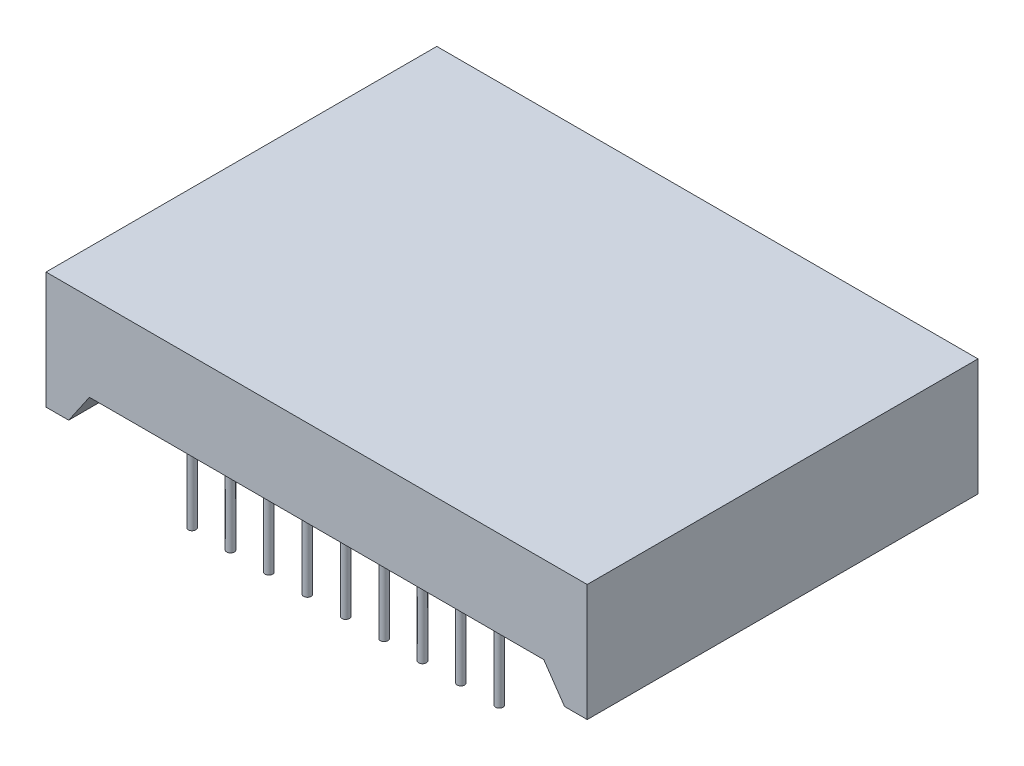
SolidWorks part; units mm, degrees
ref_plane "Front" through (0, 0, 0) normal (0, 0, 1) x (1, 0, 0)
ref_plane "Top" through (0, 0, 0) normal (0, 1, 0) x (1, 0, 0)
ref_plane "Right" through (0, 0, 0) normal (1, 0, 0) x (0, 0, -1)
sketch "Эскиз1" plane through (0, 0, 0) normal (0, 1, 0) x (1, 0, 0)
  line L0 (0, 109.8696) -> (0, -113.1116) construction
  line L1 (-69.1401, 0) -> (59.6618, 0) construction
  line L3 (17.9, -12.925) -> (-17.9, -12.925)
  line L4 (17.9, -12.925) -> (17.9, 12.925)
  line L5 (17.9, 12.925) -> (-17.9, 12.925)
  line L6 (-17.9, -12.925) -> (-17.9, 12.925)
  line L7 (17.9, -12.925) -> (-17.9, 12.925) construction
  line L8 (17.9, 12.925) -> (-17.9, -12.925) construction
  circle A0 centre (-10.16, -11) radius 0.25
  circle A1 centre (-7.62, -11) radius 0.25
  circle A2 centre (-5.08, -11) radius 0.25
  circle A3 centre (-2.54, -11) radius 0.25
  circle A4 centre (0, -11) radius 0.25
  circle A5 centre (2.54, -11) radius 0.25
  circle A6 centre (5.08, -11) radius 0.25
  circle A7 centre (7.62, -11) radius 0.25
  circle A8 centre (10.16, -11) radius 0.25
  circle A9 centre (10.16, 11) radius 0.25
  circle A10 centre (7.62, 11) radius 0.25
  circle A11 centre (5.08, 11) radius 0.25
  circle A12 centre (2.54, 11) radius 0.25
  circle A13 centre (0, 11) radius 0.25
  circle A14 centre (-2.54, 11) radius 0.25
  circle A15 centre (-5.08, 11) radius 0.25
  circle A16 centre (-7.62, 11) radius 0.25
  circle A17 centre (-10.16, 11) radius 0.25
  point P5 (0, 0)
  point P10 (0, 0)
  point P47 (0, 0)
  point P48 (0, 0)
  point P49 (0, 0)
  point P50 (0, 0)
  dimension "D3" = 0.5
  dimension "D1" = 25.85
  dimension "D2" = 35.8
  dimension "D5" = 11
  dimension "D6" = 7.74
  dimension "D4" = 9
extrude "Бобышка-Вытянуть1" add sketch "Эскиз1" along normal blind 7.74 contours L6 L3 L4 L5 A16 A14 A12 A10 A0 A1 A2 A3 A4 A5 A6 A7 A8 A9 A11 A13 A15 A17 | A0 | A1 | A2 | A3 | A4 | A5 | A6 | A7 | A8 | A17 | A16 | A15 | A14 | A13 | A12 | A11 | A10 | A9 region at (0, 0, 0)
sketch "Эскиз2" plane through (0, 0, 12.925) normal (0, 0, 1) x (1, 0, 0)
  line L0 (-17.9, 7.74) -> (-17.9, 0) construction
  line L1 (-16.4, 0) -> (-15.0276, 2)
  line L2 (-15.0276, 2) -> (15.0276, 2)
  line L3 (0, 0) -> (0, 13.6727) construction
  line L5 (16.4, 0) -> (15.0276, 2)
  point P6 (0, 0)
  point P7 (0, 0)
  point P8 (0, 0)
  point P10 (0, 0)
  point P14 (0, 2)
  dimension "D1" = 1.5
  dimension "D2" = 2
extrude "Вырез-Вытянуть1" cut sketch "Эскиз2" against normal through all and the other way through all
extrude "Бобышка-Вытянуть2" add sketch "Эскиз1<4>" against normal blind 4 and the other way up to next contours A0 | A1 | A2 | A3 | A4 | A5 | A6 | A7 | A8 | A17 | A16 | A15 | A14 | A13 | A12 | A11 | A10 | A9
sketch "Эскиз1<4>" plane through (0, 0, 0) normal (0, 1, 0) x (1, 0, 0) same geometry as "Эскиз1"
